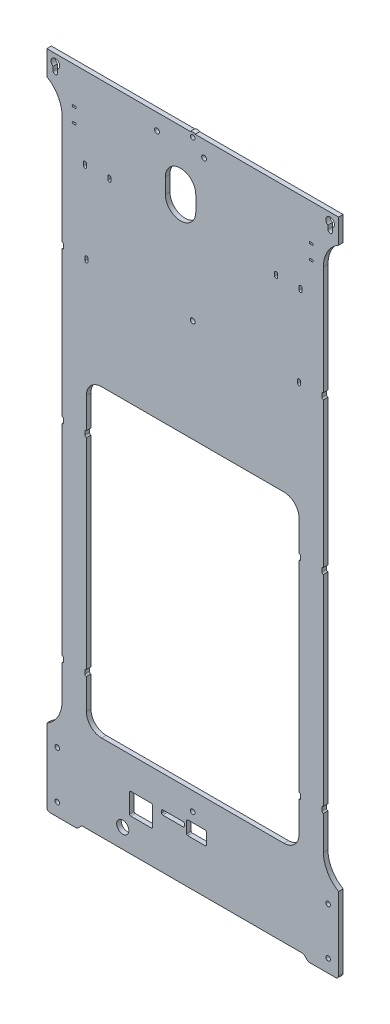
SolidWorks part; units mm, degrees
material "6061-T6 Black anodised"
ref_plane "Front Plane" through (0, 0, 0) normal (0, 0, 1) x (1, 0, 0)
ref_plane "Top Plane" through (0, 0, 0) normal (0, 1, 0) x (1, 0, 0)
ref_plane "Right Plane" through (0, 0, 0) normal (1, 0, 0) x (0, 0, -1)
sketch "Sketch1" plane through (0, 0, 0) normal (0, 0, 1) x (1, 0, 0)
  line L0 (89.02, 0) -> (-89.02, 0) construction
  line L1 (95.92, 394.5) -> (-95.92, 394.5)
  line L2 (95.92, 394.5) -> (95.92, -36.5)
  line L3 (72.92, -36.5) -> (-72.92, -36.5)
  line L4 (-95.92, 394.5) -> (-95.92, -36.5)
  line L5 (95.92, 394.5) -> (-95.92, -36.5) construction
  line L6 (95.92, -36.5) -> (-95.92, 394.5) construction
  line L7 (-90.52, -31) -> (-90.52, -28.5767) construction
  line L8 (-90.32, 384) -> (90.32, 384) construction
  line L9 (0, 384) -> (0, 0) construction
  line L10 (-87.52, -31) -> (-87.52, -28.5767) construction
  line L11 (-90.52, 0) -> (-90.52, 2.4233) construction
  line L12 (-87.52, 0) -> (-87.52, 2.4233) construction
  line L13 (87.52, -31) -> (87.52, -28.5767) construction
  line L14 (90.52, -31) -> (90.52, -28.5767) construction
  line L15 (87.52, 0) -> (87.52, 2.4233) construction
  line L16 (90.52, 0) -> (90.52, 2.4233) construction
  line L17 (88.82, 384) -> (88.82, 386.4233)
  line L18 (91.82, 384) -> (91.82, 386.4233)
  line L19 (-91.82, 384) -> (-91.82, 386.4233)
  line L20 (-88.82, 384) -> (-88.82, 386.4233)
  line L21 (95.92, -39.5) -> (75.92, -39.5)
  line L22 (75.92, -39.5) -> (72.92, -36.5)
  line L23 (-95.92, -39.5) -> (-75.92, -39.5)
  line L24 (-75.92, -39.5) -> (-72.92, -36.5)
  line L25 (-95.92, -36.5) -> (-95.92, -39.5)
  line L26 (95.92, -36.5) -> (95.92, -39.5)
  arc A0 (-90.52, 0) -> (-87.52, 0) centre (-89.02, 0) ccw
  arc A1 (87.52, 0) -> (90.52, 0) centre (89.02, 0) ccw
  arc A2 (-90.52, -31) -> (-87.52, -31) centre (-89.02, -31) ccw
  arc A4 (-91.82, 384) -> (-88.82, 384) centre (-90.32, 384) ccw
  arc A5 (88.82, 384) -> (91.82, 384) centre (90.32, 384) ccw
  arc A6 (-87.52, -28.5767) -> (-90.52, -28.5767) centre (-89.02, -26.1534) ccw construction
  circle A7 centre (-89.02, -31) radius 2.85 construction
  arc A8 (-87.52, 2.4233) -> (-90.52, 2.4233) centre (-89.02, 4.8466) ccw construction
  circle A9 centre (-89.02, 0) radius 2.85 construction
  arc A10 (90.52, -28.5767) -> (87.52, -28.5767) centre (89.02, -26.1534) ccw construction
  circle A11 centre (89.02, -31) radius 2.85 construction
  arc A12 (90.52, 2.4233) -> (87.52, 2.4233) centre (89.02, 4.8466) ccw construction
  circle A13 centre (89.02, 0) radius 2.85 construction
  arc A14 (91.82, 386.4233) -> (88.82, 386.4233) centre (90.32, 388.8466) ccw
  circle A15 centre (90.32, 384) radius 2.85 construction
  arc A16 (-88.82, 386.4233) -> (-91.82, 386.4233) centre (-90.32, 388.8466) ccw
  circle A17 centre (-90.32, 384) radius 2.85 construction
  circle A18 centre (89.02, -31) radius 1.5
  arc A19 (90.52, 0) -> (87.52, 0) centre (89.02, 0) ccw
  arc A20 (-90.52, -31) -> (-87.52, -31) centre (-89.02, -31) cw
  arc A21 (-90.52, 0) -> (-87.52, 0) centre (-89.02, 0) cw
  point P0 (0, 179)
  point P59 (-81.27, 0)
  dimension "D4" = 3
  dimension "D9" = 5.7
  dimension "D7" = 5.6
  dimension "D1" = 191.84
  dimension "D2" = 431
  dimension "D3" = 6.9
  dimension "D5" = 31
  dimension "D6" = 5.5
  dimension "D8" = 10.5
  dimension "D10" = 3
  dimension "D11" = 20
  dimension "D12" = 45
extrude "Boss-Extrude1" add sketch "Sketch1" along normal blind 3
sketch "Sketch2" plane through (0, 0, 3) normal (0, 0, 1) x (1, 0, 0)
  line L0 (-95.92, 394.5) -> (-95.92, -39.5) construction
  line L1 (-95.92, 10.5) -> (-85.92, 10.5)
  line L2 (-95.92, 10.5) -> (-95.92, 378.5)
  line L3 (-95.92, 378.5) -> (-85.92, 378.5)
  line L4 (-85.92, 10.5) -> (-85.92, 378.5)
  line L5 (95.92, -39.5) -> (95.92, 394.5) construction
  line L6 (95.92, 10.5) -> (85.92, 10.5)
  line L7 (95.92, 10.5) -> (95.92, 378.5)
  line L8 (95.92, 378.5) -> (85.92, 378.5)
  line L9 (85.92, 10.5) -> (85.92, 378.5)
  line L10 (95.92, 394.5) -> (-95.92, 394.5) construction
  line L11 (-72.92, -36.5) -> (72.92, -36.5) construction
  dimension "D1" = 16
  dimension "D2" = 47
  dimension "D3" = 10
extrude "Cut-Extrude1" cut sketch "Sketch2" against normal through all
fillet "Fillet1" radius 20 4 edges at (85.92, 10.5, 1.5) (-85.92, 10.5, 1.5) (85.92, 378.5, 1.5) (-85.92, 378.5, 1.5)
sketch "Sketch3" plane through (0, 0, 3) normal (0, 0, 1) x (1, 0, 0)
  line L0 (-72.92, -36.5) -> (72.92, -36.5) construction
  line L1 (95.92, 394.5) -> (-95.92, 394.5) construction
  circle A0 centre (0, 8) radius 1.5
  circle A2 centre (0, 392) radius 1.5
  dimension "D2" = 2.5
  dimension "D3" = 3
  dimension "D1" = 44.5
extrude "Cut-Extrude2" cut sketch "Sketch3" against normal through all
sketch "Sketch4" plane through (0, 0, 3) normal (0, 0, 1) x (1, 0, 0)
  line L0 (-85.92, 27.8205) -> (-85.92, 361.1795) construction
  line L1 (-69.92, 220) -> (69.92, 220)
  line L2 (-69.92, 220) -> (-69.92, 20)
  line L3 (-69.92, 20) -> (69.92, 20)
  line L4 (69.92, 220) -> (69.92, 20)
  line L5 (-69.92, 220) -> (69.92, 20) construction
  line L6 (-69.92, 20) -> (69.92, 220) construction
  circle A0 centre (0, 8) radius 1.5 construction
  point P0 (0, 120)
  dimension "D1" = 16
  dimension "D2" = 12
  dimension "D3" = 200
extrude "Cut-Extrude3" cut sketch "Sketch4" against normal through all
fillet "Fillet2" radius 10 4 edges at (69.92, 220, 1.5) (-69.92, 220, 1.5) (69.92, 20, 1.5) (-69.92, 20, 1.5)
sketch "Sketch5" plane through (0, 0, 3) normal (0, 0, 1) x (1, 0, 0)
  line L0 (-46, 8.2274) -> (-46, -20.9664) construction
  line L6 (-41.5, -0.8) -> (-26.5, -0.8)
  line L7 (-41.5, -0.8) -> (-41.5, -14.9)
  line L8 (-41.5, -14.9) -> (-26.5, -14.9)
  line L9 (-26.5, -0.8) -> (-26.5, -14.9)
  line L10 (-20.5, -0.8) -> (-5.5, -0.8)
  line L11 (-20.5, -0.8) -> (-20.5, -3.8)
  line L12 (-20.5, -3.8) -> (-5.5, -3.8)
  line L13 (-5.5, -0.8) -> (-5.5, -3.8)
  line L14 (-4, 1.7) -> (9, 1.7)
  line L15 (-4, 1.7) -> (-4, -7.3)
  line L16 (-4, -7.3) -> (9, -7.3)
  line L17 (9, 1.7) -> (9, -7.3)
  circle A1 centre (0, 8) radius 1.5 construction
  dimension "D3" = 2.5
  dimension "D2" = 8.8
  dimension "D5" = 46
  dimension "D6" = 4.5
  dimension "D7" = 15
  dimension "D8" = 25.5
  dimension "D9" = 15
  dimension "D10" = 42
  dimension "D11" = 13
  dimension "D12" = 14.1
  dimension "D13" = 3
  dimension "D14" = 9
extrude "Cut-Extrude4" cut sketch "Sketch5" against normal through all
fillet "Fillet3" radius 0.8 12 edges at (9, -7.3, 1.5) (9, 1.7, 1.5) (-4, 1.7, 1.5) (-4, -7.3, 1.5) (-5.5, -3.8, 1.5) (-5.5, -0.8, 1.5) (-20.5, -0.8, 1.5) (-20.5, -3.8, 1.5) (-26.5, -14.9, 1.5) (-26.5, -0.8, 1.5) (-41.5, -0.8, 1.5) (-41.5, -14.9, 1.5)
sketch "Sketch6" plane through (0, 0, 3) normal (0, 0, 1) x (1, 0, 0)
  circle A0 centre (-46, -23.8) radius 4
  circle A1 centre (0, 8) radius 1.5 construction
  dimension "D2" = 8
  dimension "D3" = 31.8
  dimension "D1" = 46
extrude "Cut-Extrude5" cut sketch "Sketch6" against normal through all
sketch "Sketch7" plane through (0, 0, 3) normal (0, 0, 1) x (1, 0, 0)
  line L0 (0, -35.055) -> (-4.8534, -39.9081)
  line L1 (6.0015, -39.9081) -> (0.8516, -35.055)
  line L2 (-7.2622, -33.0882) -> (7.8165, -33.0882)
  line L3 (8.077, -32.9782) -> (11.0039, -30.0512)
  line L4 (10.2253, -29.347) -> (-7.2622, -29.347)
  line L5 (-14.4113, -36.4965) -> (-14.4098, -53.9837)
  line L6 (-13.7057, -54.7607) -> (-10.7801, -51.8338)
  line L7 (-10.6686, -51.5749) -> (-10.67, -36.4965)
  line L8 (8.1139, -55.2833) -> (-6.9645, -55.2833)
  line L9 (-7.2249, -55.3948) -> (-10.1519, -58.3217)
  line L10 (-9.3733, -59.0259) -> (8.1139, -59.0259)
  line L11 (15.2633, -51.8752) -> (15.2619, -34.3893)
  line L12 (14.5577, -33.6121) -> (11.6308, -36.5391)
  line L13 (11.5207, -36.798) -> (11.5218, -51.8752)
  spline S0 degree 3 poles (0.4439, -34.8701) (0.3912, -34.8752) (0.2828, -34.8857) (0.1286, -34.9495) (0.0426, -35.02) (0, -35.055) knots 0 0 0 0 0.322338 0.663828 1 1 1 1
  spline S1 degree 3 poles (-4.8534, -39.9081) (-4.8579, -39.9123) (-4.8667, -39.9205) (-4.8791, -39.9329) (-5.3375, -40.4392) (-6.231, -41.4846) (-7.3312, -43.289) (-7.8887, -46.1117) (-6.8483, -49.6491) (-3.8783, -52.5981) (0.2577, -53.8719) (4.5569, -52.8137) (7.7118, -49.6441) (8.7217, -46.1226) (8.2109, -43.3277) (7.2971, -41.454) (6.4234, -40.4116) (6.0015, -39.9081) knots 0 0 0 0 0.000489 0.000958 0.001407 0.055151 0.111018 0.168413 0.280621 0.389777 0.490762 0.614387 0.723194 0.83533 0.891393 0.947551 1 1 1 1
  spline S2 degree 3 poles (0.8516, -35.055) (0.8125, -35.0211) (0.7352, -34.9541) (0.5954, -34.8849) (0.4944, -34.875) (0.4439, -34.8701) knots 0 0 0 0 0.338885 0.669777 1 1 1 1
  spline S3 degree 3 poles (7.8165, -33.0882) (7.8386, -33.0865) (7.882, -33.0833) (7.9472, -33.0756) (7.9964, -33.0496) (8.0324, -33.0241) (8.0557, -33.0007) (8.07, -32.9856) (8.077, -32.9782) knots 0 0 0 0 0.227493 0.445972 0.663373 0.787115 0.896006 1 1 1 1
  spline S4 degree 3 poles (11.0039, -30.0512) (11.0329, -30.0119) (11.0909, -29.9332) (11.1149, -29.785) (11.0877, -29.6491) (11.0204, -29.5396) (10.9299, -29.4607) (10.7969, -29.4113) (10.6368, -29.379) (10.4517, -29.3457) (10.3213, -29.3482) (10.25, -29.3467) (10.2377, -29.3461) (10.2294, -29.3467) (10.2253, -29.347) knots 0 0 0 0 0.104345 0.208931 0.313565 0.397995 0.482811 0.567894 0.701187 0.836715 0.973247 0.982163 0.991064 1 1 1 1
  spline S5 degree 3 poles (-7.2622, -29.347) (-8.5111, -29.5465) (-10.9772, -29.9405) (-13.8177, -32.781) (-14.2117, -35.2473) (-14.4113, -36.4965) knots 0 0 0 0 0.336154 0.663772 1 1 1 1
  spline S6 degree 3 poles (-14.4098, -53.9837) (-14.4101, -53.9877) (-14.4107, -53.9955) (-14.4101, -54.0074) (-14.4085, -54.0786) (-14.4116, -54.2092) (-14.3778, -54.3947) (-14.348, -54.5555) (-14.2965, -54.6876) (-14.2178, -54.7779) (-14.1086, -54.8459) (-13.9724, -54.8732) (-13.8239, -54.8488) (-13.7451, -54.7901) (-13.7057, -54.7607) knots 0 0 0 0 0.008622 0.017031 0.025643 0.162638 0.298245 0.431901 0.516392 0.601007 0.685957 0.790142 0.895037 1 1 1 1
  spline S7 degree 3 poles (-10.7801, -51.8338) (-10.7711, -51.8245) (-10.7536, -51.8064) (-10.7264, -51.7794) (-10.6977, -51.7438) (-10.6778, -51.6947) (-10.6682, -51.6355) (-10.6685, -51.5956) (-10.6686, -51.5749) knots 0 0 0 0 0.131285 0.25763 0.390972 0.594165 0.788898 1 1 1 1
  spline S8 degree 3 poles (-10.67, -36.4965) (-10.5818, -35.8926) (-10.4093, -34.7122) (-9.0474, -33.3492) (-7.8666, -33.1766) (-7.2622, -33.0882) knots 0 0 0 0 0.33841 0.661392 1 1 1 1
  spline S9 degree 3 poles (-6.9645, -55.2833) (-6.9836, -55.284) (-7.0187, -55.2854) (-7.0727, -55.2938) (-7.117, -55.3142) (-7.157, -55.3379) (-7.1915, -55.3639) (-7.2134, -55.3842) (-7.2249, -55.3948) knots 0 0 0 0 0.196746 0.361608 0.557262 0.692766 0.839563 1 1 1 1
  spline S10 degree 3 poles (-10.1519, -58.3217) (-10.1809, -58.361) (-10.2389, -58.4397) (-10.2629, -58.5879) (-10.2357, -58.7239) (-10.1681, -58.8333) (-10.0777, -58.912) (-9.9452, -58.9619) (-9.7851, -58.9945) (-9.6, -59.0248) (-9.4695, -59.0303) (-9.3981, -59.025) (-9.3857, -59.0257) (-9.3774, -59.0258) (-9.3733, -59.0259) knots 0 0 0 0 0.104385 0.20895 0.313569 0.398093 0.483012 0.567612 0.700915 0.836485 0.973043 0.982112 0.991066 1 1 1 1
  spline S11 degree 3 poles (8.1139, -59.0259) (9.3629, -58.8263) (11.8293, -58.432) (14.6704, -55.5912) (15.064, -53.1244) (15.2633, -51.8752) knots 0 0 0 0 0.336157 0.663806 1 1 1 1
  spline S12 degree 3 poles (15.2619, -34.3893) (15.2622, -34.3852) (15.2628, -34.3769) (15.2621, -34.3644) (15.2606, -34.293) (15.2632, -34.1626) (15.2298, -33.9775) (15.198, -33.8174) (15.148, -33.6849) (15.0694, -33.5945) (14.9599, -33.5269) (14.8239, -33.4997) (14.6754, -33.5241) (14.597, -33.5828) (14.5577, -33.6121) knots 0 0 0 0 0.008953 0.017947 0.027021 0.163491 0.298949 0.432165 0.516776 0.601601 0.686035 0.790672 0.895263 1 1 1 1
  spline S13 degree 3 poles (11.6308, -36.5391) (11.6212, -36.5483) (11.6023, -36.5664) (11.5737, -36.5942) (11.5433, -36.6274) (11.5265, -36.6769) (11.5219, -36.7355) (11.5211, -36.7763) (11.5207, -36.798) knots 0 0 0 0 0.134582 0.264928 0.404991 0.586048 0.77989 1 1 1 1
  spline S14 degree 3 poles (11.5218, -51.8752) (11.4339, -52.4792) (11.262, -53.6599) (9.8992, -55.0226) (8.7183, -55.195) (8.1139, -55.2833) knots 0 0 0 0 0.338406 0.661372 1 1 1 1
extrude "Cut-Extrude6" [suppressed] cut sketch "Sketch7" against normal through all
sketch "Sketch8" plane through (0, 0, 3) normal (0, 0, 1) x (1, 0, 0)
  line L0 (-13.1975, 364.095) -> (13.1975, 364.095) construction
  line L1 (-15.5, 383.9) -> (15.5, 383.9) construction
  line L2 (-15.5, 383.9) -> (-15.5, 352.9) construction
  line L3 (-15.5, 352.9) -> (15.5, 352.9) construction
  line L4 (15.5, 383.9) -> (15.5, 352.9) construction
  line L5 (-15.5, 383.9) -> (15.5, 352.9) construction
  line L6 (-15.5, 352.9) -> (15.5, 383.9) construction
  line L7 (-8, 350.4) -> (-8, 360.4) construction
  line L8 (-21, 347.4) -> (-21, 389.4) construction
  line L9 (-21, 389.4) -> (21, 389.4) construction
  line L10 (21, 347.4) -> (21, 389.4) construction
  line L11 (-21, 347.4) -> (21, 389.4) construction
  line L12 (-21, 389.4) -> (21, 347.4) construction
  line L13 (0, 368.4) -> (0, 392) construction
  line L15 (-18, 350.4) -> (-18, 360.4)
  line L16 (2, 350.4) -> (2, 360.4)
  line L17 (0, 368.4) -> (0, 364.095) construction
  line L23 (59.92, 220) -> (-59.92, 220) construction
  line L32 (1.5, 368.4) -> (-1.5, 368.4) construction
  line L35 (-23.5, 383.9) -> (7.5, 383.9) construction
  circle A0 centre (-15.5, 383.9) radius 1.6 construction
  circle A1 centre (15.5, 383.9) radius 1.6 construction
  circle A2 centre (15.5, 352.9) radius 1.6 construction
  circle A3 centre (-15.5, 352.9) radius 1.6 construction
  circle A4 centre (0, 392) radius 1.5 construction
  arc A6 (-18, 350.4) -> (2, 350.4) centre (-8, 350.4) ccw
  arc A7 (2, 360.4) -> (-18, 360.4) centre (-8, 360.4) ccw
  circle A8 centre (0, 287.5) radius 67.5 construction
  circle A9 centre (0, 287.5) radius 1.6
  circle A13 centre (7.5, 383.9) radius 1.6
  circle A14 centre (-23.5, 383.9) radius 1.6
  point P0 (0, 368.4)
  point P9 (0, 368.4)
  point P24 (-8, 355.4)
  point P56 (20, 368.4)
  dimension "D2" = 3.2
  dimension "D11" = 10
  dimension "D14" = 3.2
  dimension "D15" = 135
  dimension "D10" = 10
  dimension "D1" = 31
  dimension "D4" = 2.6
  dimension "D6" = 4.305
  dimension "D7" = 23.6
  dimension "D12" = 15.5
  dimension "D13" = 23.5
  dimension "D19" = 6
  dimension "D20" = 3
extrude "Cut-Extrude7" cut sketch "Sketch8" against normal through all
sketch "Sketch9" plane through (0, 0, 3) normal (0, 0, 1) x (1, 0, 0)
  line L0 (95.92, 394.5) -> (-95.92, 394.5) construction
  line L1 (-1.6583, 394.5) -> (1.6583, 394.5)
  arc A0 (1.6583, 394.5) -> (-1.6583, 394.5) centre (0, 392) ccw
  dimension "D1" = 3
extrude "Boss-Extrude2" add sketch "Sketch9" against normal up to surface (3 mm away) up to face at (-21.9, 383.9, 0)
sketch "Sketch10" plane through (0, 0, 3) normal (0, 0, 1) x (1, 0, 0)
  line L0 (0, 392) -> (0, 370.5) construction
  line L1 (-77.92, 370.5) -> (77.92, 370.5) construction
  line L2 (-85.92, 27.8205) -> (-85.92, 361.1795) construction
  line L3 (-1.6583, 394.5) -> (-95.92, 394.5) construction
  line L4 (-77.92, 370.5) -> (-47.92, 370.5) construction
  line L5 (-78.57, 370.5) -> (-77.27, 370.5) construction
  line L6 (-78.57, 371.15) -> (-77.27, 371.15)
  line L7 (-78.57, 369.85) -> (-77.27, 369.85)
  line L8 (-78.57, 361) -> (-77.27, 361) construction
  line L9 (-78.57, 361.65) -> (-77.27, 361.65)
  line L10 (-78.57, 360.35) -> (-77.27, 360.35)
  line L17 (77.27, 370.5) -> (78.57, 370.5) construction
  line L18 (77.27, 371.15) -> (78.57, 371.15)
  line L19 (77.27, 369.85) -> (78.57, 369.85)
  line L20 (77.27, 361) -> (78.57, 361) construction
  line L21 (77.27, 361.65) -> (78.57, 361.65)
  line L22 (77.27, 360.35) -> (78.57, 360.35)
  circle A0 centre (-77.92, 370.5) radius 0.65 construction
  circle A1 centre (-77.92, 361) radius 0.65 construction
  circle A2 centre (77.92, 370.5) radius 0.65 construction
  circle A3 centre (77.92, 361) radius 0.65 construction
  arc A6 (-78.57, 371.15) -> (-78.57, 369.85) centre (-78.57, 370.5) ccw
  arc A7 (-77.27, 369.85) -> (-77.27, 371.15) centre (-77.27, 370.5) ccw
  arc A8 (-78.57, 361.65) -> (-78.57, 360.35) centre (-78.57, 361) ccw
  arc A9 (-77.27, 360.35) -> (-77.27, 361.65) centre (-77.27, 361) ccw
  arc A14 (77.27, 371.15) -> (77.27, 369.85) centre (77.27, 370.5) ccw
  arc A15 (78.57, 369.85) -> (78.57, 371.15) centre (78.57, 370.5) ccw
  arc A16 (77.27, 361.65) -> (77.27, 360.35) centre (77.27, 361) ccw
  arc A17 (78.57, 360.35) -> (78.57, 361.65) centre (78.57, 361) ccw
  point P24 (-77.92, 370.5)
  point P29 (-77.92, 361)
  point P50 (77.92, 370.5)
  point P57 (77.92, 361)
  dimension "D2" = 1.3
  dimension "D1" = 9.5
  dimension "D3" = 8
  dimension "D4" = 24
extrude "Cut-Extrude8" cut sketch "Sketch10" against normal through all
sketch "Sketch11" plane through (0, 0, 3) normal (0, 0, 1) x (1, 0, 0)
  line L0 (85.92, 189) -> (85.92, 187) construction
  line L1 (86.92, 189) -> (86.92, 187)
  line L2 (84.92, 189) -> (84.92, 187)
  line L3 (0, 0) -> (0, 406.4665) construction
  line L4 (69.92, 189) -> (69.92, 187) construction
  line L5 (70.92, 189) -> (70.92, 187)
  line L6 (-85.92, 53) -> (-85.92, 51) construction
  line L7 (68.92, 189) -> (68.92, 187)
  line L8 (85.92, 288.5) -> (85.92, 286.5) construction
  line L9 (86.92, 288.5) -> (86.92, 286.5)
  line L10 (84.92, 288.5) -> (84.92, 286.5)
  line L11 (69.92, 288.5) -> (69.92, 286.5) construction
  line L12 (70.92, 288.5) -> (70.92, 286.5)
  line L13 (68.92, 288.5) -> (68.92, 286.5)
  line L14 (59.92, 220) -> (-59.92, 220) construction
  line L15 (85.92, 53) -> (85.92, 51) construction
  line L16 (86.92, 53) -> (86.92, 51)
  line L17 (84.92, 53) -> (84.92, 51)
  line L18 (69.92, 53) -> (69.92, 51) construction
  line L19 (70.92, 53) -> (70.92, 51)
  line L20 (68.92, 53) -> (68.92, 51)
  line L21 (-86.92, 53) -> (-86.92, 51)
  line L22 (85.92, 189) -> (69.92, 189) construction
  line L23 (85.92, 361.1795) -> (85.92, 27.8205) construction
  line L24 (-84.92, 53) -> (-84.92, 51)
  line L25 (-69.92, 53) -> (-69.92, 51) construction
  line L26 (-70.92, 53) -> (-70.92, 51)
  line L27 (-59.92, 20) -> (59.92, 20) construction
  line L28 (-68.92, 53) -> (-68.92, 51)
  line L29 (-85.92, 189) -> (-85.92, 187) construction
  line L30 (-86.92, 189) -> (-86.92, 187)
  line L31 (-84.92, 189) -> (-84.92, 187)
  line L32 (-69.92, 189) -> (-69.92, 187) construction
  line L33 (-70.92, 189) -> (-70.92, 187)
  line L34 (-68.92, 189) -> (-68.92, 187)
  line L35 (-85.92, 288.5) -> (-85.92, 286.5) construction
  line L36 (-86.92, 288.5) -> (-86.92, 286.5)
  line L37 (-84.92, 288.5) -> (-84.92, 286.5)
  line L38 (-69.92, 288.5) -> (-69.92, 286.5) construction
  line L39 (-70.92, 288.5) -> (-70.92, 286.5)
  line L40 (-68.92, 288.5) -> (-68.92, 286.5)
  line L41 (70.8127, 342) -> (70.8127, 340) construction
  line L42 (71.8127, 342) -> (71.8127, 340)
  line L43 (69.8127, 342) -> (69.8127, 340)
  line L44 (54.8127, 342) -> (54.8127, 340) construction
  line L45 (55.8127, 342) -> (55.8127, 340)
  line L46 (53.8127, 342) -> (53.8127, 340)
  line L47 (-70.8127, 342) -> (-70.8127, 340) construction
  line L48 (-71.8127, 342) -> (-71.8127, 340)
  line L49 (-69.8127, 342) -> (-69.8127, 340)
  line L50 (-54.8127, 342) -> (-54.8127, 340) construction
  line L51 (-55.8127, 342) -> (-55.8127, 340)
  line L52 (-53.8127, 342) -> (-53.8127, 340)
  arc A0 (86.92, 189) -> (84.92, 189) centre (85.92, 189) ccw
  arc A1 (84.92, 187) -> (86.92, 187) centre (85.92, 187) ccw
  arc A2 (70.92, 189) -> (68.92, 189) centre (69.92, 189) ccw
  arc A3 (68.92, 187) -> (70.92, 187) centre (69.92, 187) ccw
  arc A4 (86.92, 288.5) -> (84.92, 288.5) centre (85.92, 288.5) ccw
  arc A5 (84.92, 286.5) -> (86.92, 286.5) centre (85.92, 286.5) ccw
  arc A6 (70.92, 288.5) -> (68.92, 288.5) centre (69.92, 288.5) ccw
  arc A7 (68.92, 286.5) -> (70.92, 286.5) centre (69.92, 286.5) ccw
  arc A8 (86.92, 53) -> (84.92, 53) centre (85.92, 53) ccw
  arc A9 (84.92, 51) -> (86.92, 51) centre (85.92, 51) ccw
  arc A10 (70.92, 53) -> (68.92, 53) centre (69.92, 53) ccw
  arc A11 (68.92, 51) -> (70.92, 51) centre (69.92, 51) ccw
  arc A12 (-86.92, 53) -> (-84.92, 53) centre (-85.92, 53) cw
  arc A13 (-84.92, 51) -> (-86.92, 51) centre (-85.92, 51) cw
  arc A14 (-70.92, 53) -> (-68.92, 53) centre (-69.92, 53) cw
  arc A15 (-68.92, 51) -> (-70.92, 51) centre (-69.92, 51) cw
  arc A16 (-86.92, 189) -> (-84.92, 189) centre (-85.92, 189) cw
  arc A17 (-84.92, 187) -> (-86.92, 187) centre (-85.92, 187) cw
  arc A18 (-70.92, 189) -> (-68.92, 189) centre (-69.92, 189) cw
  arc A19 (-68.92, 187) -> (-70.92, 187) centre (-69.92, 187) cw
  arc A20 (-86.92, 288.5) -> (-84.92, 288.5) centre (-85.92, 288.5) cw
  arc A21 (-84.92, 286.5) -> (-86.92, 286.5) centre (-85.92, 286.5) cw
  arc A22 (-70.92, 288.5) -> (-68.92, 288.5) centre (-69.92, 288.5) cw
  arc A23 (-68.92, 286.5) -> (-70.92, 286.5) centre (-69.92, 286.5) cw
  arc A24 (71.8127, 342) -> (69.8127, 342) centre (70.8127, 342) ccw
  arc A25 (69.8127, 340) -> (71.8127, 340) centre (70.8127, 340) ccw
  arc A26 (55.8127, 342) -> (53.8127, 342) centre (54.8127, 342) ccw
  arc A27 (53.8127, 340) -> (55.8127, 340) centre (54.8127, 340) ccw
  arc A28 (77.27, 361.65) -> (77.27, 360.35) centre (77.27, 361) ccw construction
  arc A29 (-71.8127, 342) -> (-69.8127, 342) centre (-70.8127, 342) cw
  arc A30 (-69.8127, 340) -> (-71.8127, 340) centre (-70.8127, 340) cw
  arc A31 (-55.8127, 342) -> (-53.8127, 342) centre (-54.8127, 342) cw
  arc A32 (-53.8127, 340) -> (-55.8127, 340) centre (-54.8127, 340) cw
  point P2 (85.92, 188)
  point P12 (69.92, 188)
  point P19 (85.92, 287.5)
  point P26 (69.92, 287.5)
  point P35 (85.92, 52)
  point P42 (69.92, 52)
  point P49 (0, 287.5)
  point P58 (-85.92, 52)
  point P65 (-69.92, 52)
  point P72 (-85.92, 188)
  point P79 (-69.92, 188)
  point P86 (-85.92, 287.5)
  point P93 (-69.92, 287.5)
  point P100 (70.8127, 341)
  point P105 (54.8127, 341)
  point P112 (76.62, 361)
  point P118 (-70.8127, 341)
  point P125 (-54.8127, 341)
  dimension "D6" = 32
  dimension "D1" = 2
  dimension "D2" = 2
  dimension "D3" = 32
  dimension "D4" = 16
  dimension "D5" = 2
  dimension "D7" = 20
  dimension "D8" = 16
extrude "Cut-Extrude9" cut sketch "Sketch11" against normal through all
fillet "Fillet5" radius 2 6 edges at (72.92, -36.5, 1.5) (75.92, -39.5, 1.5) (95.92, -39.5, 1.5) (-72.92, -36.5, 1.5) (-75.92, -39.5, 1.5) (-95.92, -39.5, 1.5)
sketch "Sketch12" plane through (0, 0, 3) normal (0, 0, 1) x (1, 0, 0)
  line L0 (-88.02, 7.7) -> (-81.17, 7.7)
  line L1 (-88.02, -23.3) -> (-81.17, -23.3)
  line L2 (-88.02, 7.7) -> (-88.02, -3.5)
  line L3 (-88.02, -3.5) -> (-81.17, -3.5)
  line L4 (-88.02, -23.3) -> (-88.02, -34.5)
  line L5 (-81.17, 7.7) -> (-81.17, -3.5)
  line L6 (-95.92, 10.5) -> (-95.92, -37.5) construction
  line L7 (-88.02, -34.5) -> (-81.17, -34.5)
  line L8 (-81.17, -23.3) -> (-81.17, -34.5)
  line L9 (-81.27, 0) -> (-81.27, -31) construction
  circle A0 centre (0, 8) radius 1.5 construction
  point P8 (-81.27, 0)
  point P15 (-81.27, -31)
  dimension "D5" = 8
  dimension "D1" = 3.5
  dimension "D2" = 6.85
  dimension "D3" = 7.9
  dimension "D4" = 11.2
  dimension "D7" = 31
  dimension "D6" = 2
extrude "Cut-Extrude10" [suppressed] cut sketch "Sketch12" against normal through all
chamfer "Chamfer1" [suppressed] distance 3 angle 10
mirror "Mirror1" [suppressed] about plane through (0, 0, 0) normal (1, 0, 0)
